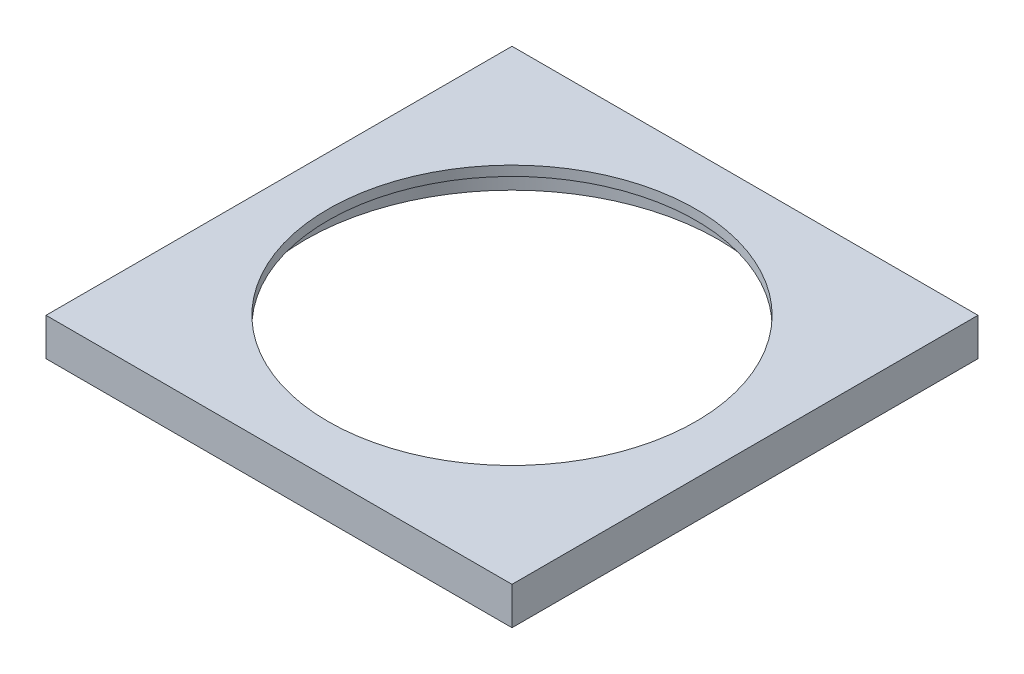
SolidWorks part; units mm, degrees
ref_plane "Ebene vorne" through (0, 0, 0) normal (0, 0, 1) x (1, 0, 0)
ref_plane "Ebene oben" through (0, 0, 0) normal (0, 1, 0) x (1, 0, 0)
ref_plane "Ebene rechts" through (0, 0, 0) normal (1, 0, 0) x (0, 0, -1)
sketch "Skizze1" plane through (0, 0, 0) normal (0, 1, 0) x (1, 0, 0)
  line L1 (-28.5, -28.5) -> (28.5, -28.5)
  line L2 (-28.5, -28.5) -> (-28.5, 28.5)
  line L3 (-28.5, 28.5) -> (28.5, 28.5)
  line L4 (28.5, -28.5) -> (28.5, 28.5)
  line L5 (-28.5, -28.5) -> (28.5, 28.5) construction
  line L6 (-28.5, 28.5) -> (28.5, -28.5) construction
  circle A0 centre (0, 0) radius 22.5
  circle A1 centre (0, 0) radius 25.25
  dimension "D1" = 45
  dimension "D4" = 50.5
  dimension "D2" = 57
  dimension "D3" = 57
extrude "Aufsatz-Linear austragen1" add sketch "Skizze1" along normal blind 3.4 contours L1 L4 L3 L2 A1 region at (-27.6939, 0, 0)
extrude "Aufsatz-Linear austragen2" add sketch "Skizze1<3>" along normal blind 1.2 from surface contours L1 L4 L3 L2 A1 | A1 A0 region at (-27.6939, 0, 0) region at (-24.5358, 0, 0) starting at face at (0, 3.4, 25.25)
sketch "Skizze1<3>" plane through (0, 0, 0) normal (0, 1, 0) x (1, 0, 0) same geometry as "Skizze1"
